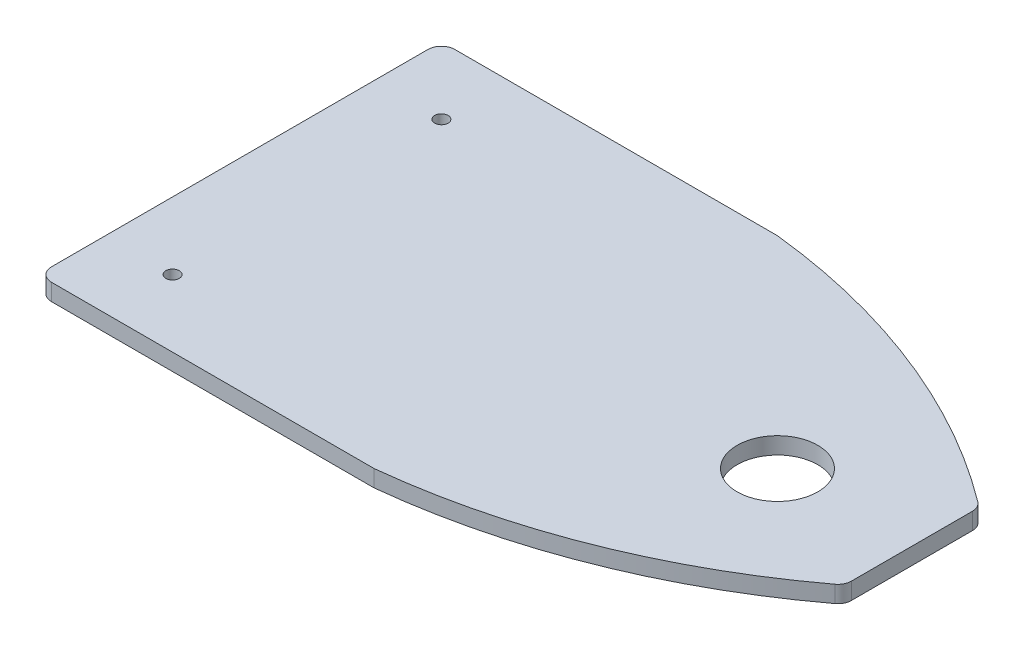
SolidWorks part; units mm, degrees
ref_plane "Front" through (0, 0, 0) normal (0, 0, 1) x (1, 0, 0)
ref_plane "Top" through (0, 0, 0) normal (0, 1, 0) x (1, 0, 0)
ref_plane "Right" through (0, 0, 0) normal (1, 0, 0) x (0, 0, -1)
sketch "Sketch1" plane through (0, 0, 0) normal (0, 1, 0) x (1, 0, 0)
  line L1 (63.5, -38.1) -> (-63.5, -38.1)
  line L2 (63.5, -38.1) -> (63.5, 38.1)
  line L3 (63.5, 38.1) -> (-63.5, 38.1)
  line L4 (-63.5, -38.1) -> (-63.5, 38.1)
  line L5 (63.5, -38.1) -> (-63.5, 38.1) construction
  line L6 (63.5, 38.1) -> (-63.5, -38.1) construction
  point P0 (0, 0)
  dimension "D1" = 76.2
  dimension "D2" = 127
extrude "Boss-Extrude1" add sketch "Sketch1" along normal blind 3.175
sketch "Sketch4" plane through (0, 3.175, 0) normal (0, 1, 0) x (1, 0, 0)
  line L0 (0, 38.1) -> (63.5, 38.1)
  line L1 (63.5, 38.1) -> (-63.5, 38.1) construction
  line L2 (63.5, 38.1) -> (63.5, 12.7)
  line L3 (63.5, -38.1) -> (63.5, 38.1) construction
  line L4 (63.5, -38.1) -> (63.5, -12.7)
  line L5 (63.5, -38.1) -> (0, -38.1)
  line L6 (-63.5, -38.1) -> (63.5, -38.1) construction
  arc A0 (0, -38.1) -> (63.5, -12.7) centre (-13.6747, 88.1616) ccw
  arc A1 (0, 38.1) -> (63.5, 12.7) centre (-13.6747, -88.1616) cw
  dimension "D3" = 127
  dimension "D4" = 127
  dimension "D1" = 25.4
  dimension "D2" = 25.4
extrude "Cut-Extrude1" cut sketch "Sketch4" against normal blind 3.175
fillet "Fillet2" radius 2.54 2 edges at (63.5, 1.5875, 12.7) (63.5, 1.5875, -12.7)
fillet "Fillet3" radius 2.54 2 edges at (-63.5, 1.5875, 38.1) (-63.5, 1.5875, -38.1)
sketch "Sketch5" plane through (0, 3.175, 0) normal (0, 1, 0) x (1, 0, 0)
  line L0 (-1.7463, 0) -> (1.7463, 0) construction
  line L1 (63.5, -11.4373) -> (63.5, 11.4373) construction
  circle A0 centre (38.1, 0) radius 7.62
  dimension "D1" = 15.24
  dimension "D2" = 25.4
extrude "Cut-Extrude2" cut sketch "Sketch5" against normal blind 3.175
sketch "Sketch6" plane through (0, 3.175, 0) normal (0, 1, 0) x (1, 0, 0)
  line L0 (0, 38.1) -> (-60.96, 38.1) construction
  line L1 (-60.96, -38.1) -> (0, -38.1) construction
  line L2 (-63.5, 35.56) -> (-63.5, -35.56) construction
  circle A0 centre (-50.8, 25.4) radius 1.27
  circle A1 centre (-50.8, -25.4) radius 1.27
  point P10 (0, 0)
  point P11 (0, 0)
  dimension "D1" = 2.54
  dimension "D2" = 2.54
  dimension "D4" = 12.7
  dimension "D3" = 12.7
  dimension "D5" = 12.7
  dimension "D6" = 12.7
extrude "Cut-Extrude3" cut sketch "Sketch6" against normal blind 3.175
